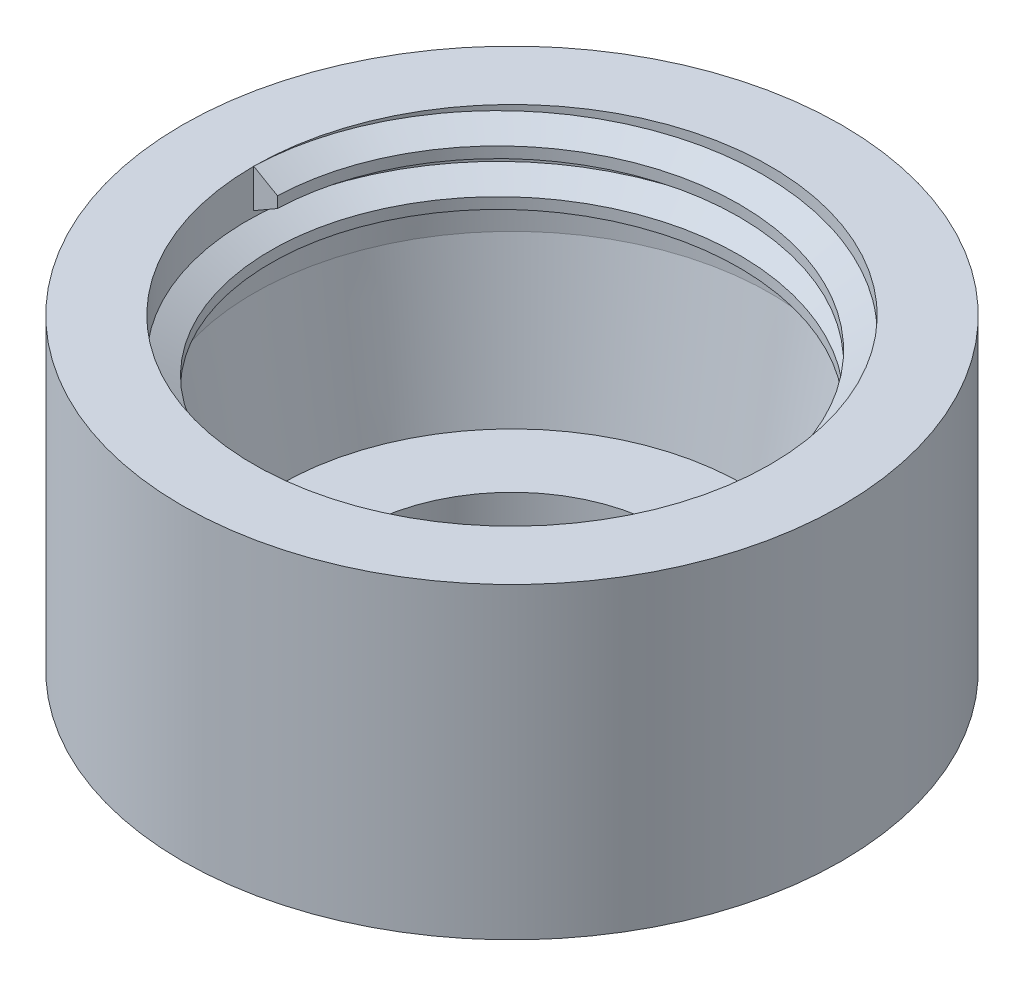
SolidWorks part; units mm, degrees
ref_plane "Front" through (0, 0, 0) normal (0, 0, 1) x (1, 0, 0)
ref_plane "Top" through (0, 0, 0) normal (0, 1, 0) x (1, 0, 0)
ref_plane "Right" through (0, 0, 0) normal (1, 0, 0) x (0, 0, -1)
sketch "Sketch1" plane through (0, 0, 0) normal (0, 1, 0) x (1, 0, 0)
  circle A0 centre (0, 0) radius 11.75
  circle A1 centre (0, 0) radius 15
extrude "Boss-Extrude1" add sketch "Sketch1" along normal blind 5
sketch "Sketch2" plane through (0, 0, 0) normal (0, 0, 1) x (1, 0, 0)
  line L0 (0, 10.906) -> (0, -7.1582) construction
  line L1 (15, 0) -> (15, -9)
  line L2 (15, -9) -> (7, -9)
  line L3 (7, -9) -> (7, -6.92)
  line L4 (7, -6.92) -> (10.5298, -6.92)
  line L5 (10.5298, -6.92) -> (11.75, 0)
  line L6 (-15, 0) -> (15, 0) construction
  line L7 (11.75, 0) -> (15, 0)
  line L8 (11.75, 0) -> (11.75, 5) construction
  point P7 (0, 0)
  point P13 (12.0543, 0)
  point P14 (11.85, 0)
  point P17 (11.75, 0)
  dimension "D1" = 100
  dimension "D2" = 7
revolve "Revolve1" add sketch "Sketch2" angle 360 about L0
thread "Thread1" pitch 2 method extrude profile "Thread Profile1" start angle 0, offset 0, length 3, pitch 2, diameter 23.5
ref_plane "Plane1" through (-11.75, 5, 0) normal (0, 0, 1) x (-1, 0, 0)
sketch "Thread Profile1" plane through (-11.75, 5, 0) normal (0, 0, 1) x (-1, 0, 0)
  line L0 (0, 0) -> (0, 2) construction
  line L11 (0, 0) -> (0, 1.75)
  line L12 (0, 1.75) -> (-1.0825, 1.125)
  line L13 (-1.0825, 1.125) -> (-1.0825, 0.625)
  line L15 (-1.0825, 0.625) -> (0, 0)
  line L17 (-1.0825, 0.875) -> (0, 0.875) construction
  point P2 (0, 0)
  dimension "Pitch" = 2
  dimension "Profile_Angle" = 60
  dimension "Profile_Land" = 0.5
  dimension "Profile_Height" = 1.0825
